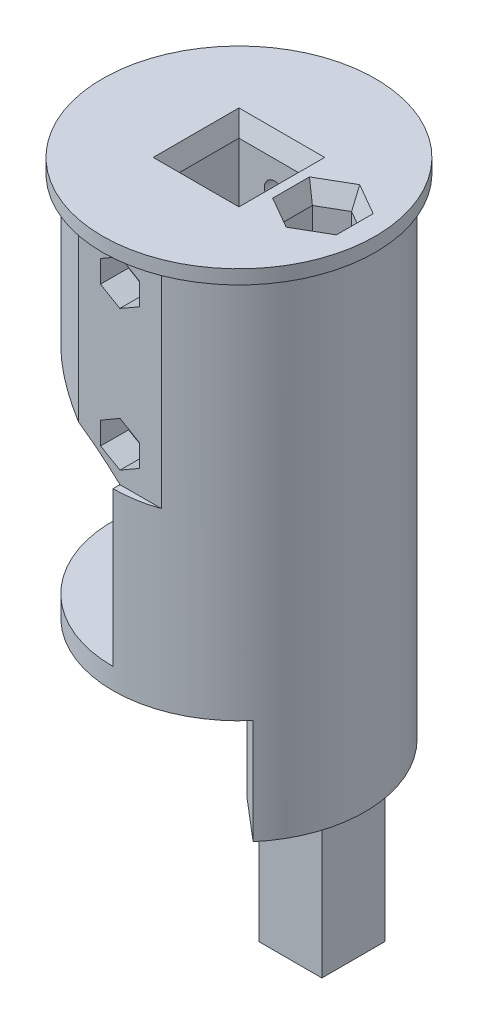
SolidWorks part; units mm, degrees
ref_plane "Спереди" through (0, 0, 0) normal (0, 0, 1) x (1, 0, 0)
ref_plane "Сверху" through (0, 0, 0) normal (0, 1, 0) x (1, 0, 0)
ref_plane "Справа" through (0, 0, 0) normal (1, 0, 0) x (0, 0, -1)
sketch "Эскиз1" plane through (0, 0, 0) normal (0, 1, 0) x (1, 0, 0)
  circle A0 centre (0, 0) radius 18
  dimension "D1" = 36
extrude "Бобышка-Вытянуть1" add sketch "Эскиз1" along normal blind 55
sketch "Эскиз2" plane through (0, 55, 0) normal (0, 1, 0) x (1, 0, 0)
  circle A0 centre (0, 0) radius 19.5
  dimension "D1" = 39
extrude "Бобышка-Вытянуть2" add sketch "Эскиз2" along normal blind 2
sketch "Эскиз3" plane through (0, 57, 0) normal (0, 1, 0) x (1, 0, 0)
  line L1 (-5.125, -5.125) -> (5.125, -5.125)
  line L2 (-5.125, -5.125) -> (-5.125, 5.125)
  line L3 (-5.125, 5.125) -> (5.125, 5.125)
  line L4 (5.125, -5.125) -> (5.125, 5.125)
  line L5 (-5.125, -5.125) -> (5.125, 5.125) construction
  line L6 (-5.125, 5.125) -> (5.125, -5.125) construction
  point P0 (0, 0)
  dimension "D1" = 10.25
extrude "Вырез-Вытянуть1" cut sketch "Эскиз3" against normal blind 40
sketch "Эскиз4" plane through (0, 0, 0) normal (0, -1, 0) x (1, 0, 0)
  line L0 (0, 0) -> (11.5702, 13.7888) construction
  line L1 (0, 0) -> (11.5702, -13.7888) construction
  line L2 (11.5702, 13.7888) -> (11.5702, -13.7888) construction
  line L3 (0, 0) -> (13.6996, 11.6756) construction
  line L5 (5.1423, -6.1284) -> (11.5702, -13.7888)
  line L6 (5.1423, -6.1284) -> (5.1423, 4.3826)
  line L7 (5.1423, 4.3826) -> (13.6996, 11.6756)
  circle A3 centre (0, 0) radius 18 construction
  arc A4 (13.6996, 11.6756) -> (11.5702, -13.7888) centre (0, 0) cw
  point P5 (11.5702, 13.7888)
  point P8 (11.5702, -13.7888)
  dimension "D1" = 100
  dimension "D2" = 3
  dimension "D3" = 10
extrude "Бобышка-Вытянуть3" add sketch "Эскиз4" along normal blind 15
sketch "Sketch1" plane through (0, -15, 0) normal (0, -1, 0) x (1, 0, 0)
  circle A0 centre (0, 0) radius 18
  arc A3 (13.6996, 11.6756) -> (11.5702, -13.7888) centre (0, 0) ccw construction
extrude "Boss-Extrude1" add sketch "Sketch1" along normal blind 20
sketch "Sketch3" plane through (0, -35, 0) normal (0, -1, 0) x (1, 0, 0)
  circle A0 centre (0, 0) radius 18
  circle A3 centre (0, 0) radius 18 construction
extrude "Boss-Extrude2" add sketch "Sketch3" along normal blind 7
sketch "Sketch4" plane through (0, -42, 0) normal (0, -1, 0) x (1, 0, 0)
  line L1 (5.1, 5.1) -> (-5.1, 5.1)
  line L2 (5.1, 5.1) -> (5.1, -5.1)
  line L3 (5.1, -5.1) -> (-5.1, -5.1)
  line L4 (-5.1, 5.1) -> (-5.1, -5.1)
  line L5 (5.1, 5.1) -> (-5.1, -5.1) construction
  line L6 (5.1, -5.1) -> (-5.1, 5.1) construction
  point P0 (0, 0)
  dimension "D1" = 10.2
  dimension "D2" = 10.2
extrude "Cut-Extrude2" cut sketch "Sketch4" against normal blind 27
sketch "Sketch6" plane through (0, 0, 0) normal (0, -1, 0) x (1, 0, 0)
  line L0 (0, 18) -> (0, -18) construction
  line L1 (0, 18) -> (0, -18)
  arc A0 (13.6996, 11.6756) -> (11.5702, -13.7888) centre (0, 0) ccw construction
  arc A1 (0, -18) -> (0, 18) centre (0, 0) cw
extrude "Cut-Extrude4" cut sketch "Sketch6" against normal blind 25
sketch "Sketch8" plane through (0, 0, 0) normal (0, -1, 0) x (1, 0, 0)
  line L0 (0, -18) -> (0, 18)
  arc A0 (0, -18) -> (0, 18) centre (0, 0) cw
  arc A1 (13.6996, 11.6756) -> (0, 18) centre (0, 0) ccw construction
extrude "Boss-Extrude3" add sketch "Sketch8" against normal blind 3
sketch "Sketch9" plane through (0, 0, 0) normal (-1, 0, 0) x (0, 0, 1)
  line L0 (-18, 3) -> (18, 25) construction
  line L2 (18, 25) -> (-18, 25)
  line L3 (18, 25) -> (18, 3)
  line L4 (18, 3) -> (-18, 3)
  line L5 (-18, 25) -> (-18, 3)
  line L6 (18, 25) -> (-18, 3) construction
  line L7 (18, 3) -> (-18, 25) construction
  point P4 (0, 14)
extrude "Cut-Extrude5" cut sketch "Sketch9" against normal blind 8
sketch "Sketch10" plane through (0, 0, 0) normal (0, -1, 0) x (1, 0, 0)
  line L0 (0, -18) -> (0, 18) construction
  line L2 (1.5, 8.7) -> (-1.5, 8.7)
  line L3 (1.5, 8.7) -> (1.5, 6.7)
  line L4 (1.5, 6.7) -> (-1.5, 6.7)
  line L5 (-1.5, 8.7) -> (-1.5, 6.7)
  line L6 (1.5, 8.7) -> (-1.5, 6.7) construction
  line L7 (1.5, 6.7) -> (-1.5, 8.7) construction
  circle A0 centre (0, 0) radius 3.7
  arc A1 (13.6996, 11.6756) -> (11.5702, -13.7888) centre (0, 0) ccw construction
  point P9 (0, 7.7)
  point P14 (0, 3.7)
  dimension "D1" = 7.4
  dimension "D2" = 2
  dimension "D3" = 3
  dimension "D4" = 4
extrude "Cut-Extrude6" cut sketch "Sketch10" against normal blind 10
sketch "Sketch11" plane through (0, -42, 0) normal (0, -1, 0) x (1, 0, 0)
  line L0 (-18, 0) -> (18, 0) construction
  circle A0 centre (0, 0) radius 18 construction
  circle A1 centre (12, 0) radius 2
  dimension "D1" = 4
  dimension "D2" = 6
extrude "Cut-Extrude7" cut sketch "Sketch11" against normal blind 102
sketch "Sketch15" plane through (0, -42, 0) normal (0, -1, 0) x (1, 0, 0)
  circle A0 centre (0, 0) radius 18
  circle A3 centre (0, 0) radius 18 construction
extrude "Cut-Extrude9" cut sketch "Sketch15" against normal blind 27
sketch "Sketch17" plane through (0, 25, 0) normal (0, -1, 0) x (1, 0, 0)
  line L2 (-18, 0) -> (14.8, 0) construction
  line L3 (14.8, 0) -> (13.8, 0) construction
  line L4 (0, 18) -> (0, -18) construction
  line L6 (5.9161, -17) -> (-5.9161, -17)
  line L7 (5.9161, 17) -> (-5.9161, 17)
  arc A0 (8, 16.1245) -> (8, -16.1245) centre (0, 0) ccw construction
  arc A1 (-5.9161, -17) -> (5.9161, -17) centre (0, 0) ccw
  arc A2 (-5.9161, 17) -> (5.9161, 17) centre (0, 0) cw
  point P14 (13.8, 0)
  point P20 (0, -17)
  point P23 (0, 17)
  dimension "D4" = 1
extrude "Cut-Extrude11" cut sketch "Sketch17" against normal blind 30
sketch "Sketch18" plane through (0, 0, -17) normal (0, 0, 1) x (1, 0, 0)
  line L0 (0, 25) -> (0, 55) construction
  line L1 (5.9161, 25) -> (-5.9161, 25) construction
  line L2 (5.9161, 55) -> (-5.9161, 55) construction
  circle A0 centre (0, 30) radius 1.5
  circle A1 centre (0, 50) radius 1.5
  point P3 (0, 40)
  dimension "D1" = 3
  dimension "D2" = 10
  dimension "D3" = 20
extrude "Cut-Extrude12" cut sketch "Sketch18" along normal through all
sketch "Sketch19" plane through (0, 0, -17) normal (0, 0, 1) x (1, 0, 0)
  circle A0 centre (0, 30) radius 3
  circle A1 centre (0, 50) radius 3
  dimension "D1" = 6
extrude "Cut-Extrude13" cut sketch "Sketch19" along normal blind 3
sketch "Sketch23" plane through (0, 3, 0) normal (0, 1, 0) x (1, 0, 0)
  line L0 (0, 18) -> (0, -18) construction
  line L1 (0, -14.4) -> (8, -14.4)
  line L2 (8, 16.1245) -> (8, -16.1245) construction
  line L3 (0, 14.4) -> (8, 14.4)
  line L4 (0, -14.4) -> (0, -18)
  line L5 (0, 14.4) -> (0, 18)
  line L6 (8, -14.4) -> (8, -16.1245)
  line L7 (8, 16.1245) -> (8, 14.4)
  arc A0 (8, 16.1245) -> (8, -16.1245) centre (0, 0) ccw construction
  arc A1 (0, -18) -> (8, -16.1245) centre (0, 0) ccw
  arc A2 (0, 18) -> (8, 16.1245) centre (0, 0) cw
  arc A3 (-5.9161, 17) -> (-5.9161, -17) centre (0, 0) ccw construction
  arc A4 (11.5702, 13.7888) -> (13.6996, -11.6756) centre (0, 0) ccw construction
  dimension "D1" = 3.6
extrude "Boss-Extrude5" add sketch "Sketch23" along normal blind 22
sketch "Sketch25" plane through (0, 0, 17) normal (0, 0, 1) x (1, 0, 0)
  line L0 (0, 55) -> (0, 25) construction
  line L1 (2.7713, 28.4) -> (2.7713, 31.6)
  line L2 (2.7713, 31.6) -> (0, 33.2)
  line L3 (0, 33.2) -> (-2.7713, 31.6)
  line L4 (-2.7713, 31.6) -> (-2.7713, 28.4)
  line L5 (-2.7713, 28.4) -> (0, 26.8)
  line L6 (0, 26.8) -> (2.7713, 28.4)
  line L7 (-5.9161, 55) -> (5.9161, 55) construction
  line L9 (-2.7821, 48.4189) -> (-0.0218, 46.8001)
  line L10 (-0.0218, 46.8001) -> (2.7603, 48.3811)
  line L11 (2.7603, 48.3811) -> (2.7821, 51.5811)
  line L12 (2.7821, 51.5811) -> (0.0218, 53.1999)
  line L13 (0.0218, 53.1999) -> (-2.7603, 51.6189)
  line L14 (-2.7603, 51.6189) -> (-2.7821, 48.4189)
  circle A0 centre (0, 30) radius 3.2 construction
  circle A1 centre (0, 50) radius 3.2 construction
  point P24 (0, 40)
  dimension "D1" = 6.4
  dimension "D2" = 20
  dimension "D3" = 10
extrude "Cut-Extrude16" cut sketch "Sketch25" against normal blind 4
sketch "Sketch26" plane through (0, 57, 0) normal (0, 1, 0) x (1, 0, 0)
  line L0 (14.8, 0) -> (5.125, 0) construction
  line L2 (8.4493, -2.05) -> (12, -4.1)
  line L3 (12, -4.1) -> (15.5507, -2.05)
  line L4 (15.5507, -2.05) -> (15.5507, 2.05)
  line L5 (15.5507, 2.05) -> (12, 4.1)
  line L6 (12, 4.1) -> (8.4493, 2.05)
  line L7 (5.125, -5.125) -> (5.125, 5.125) construction
  line L8 (8.4493, 2.05) -> (8.4493, -2.05)
  circle A0 centre (12, 0) radius 4.1 construction
  point P2 (15.5507, 0)
  dimension "D1" = 8.2
extrude "Cut-Extrude17" cut sketch "Sketch26" against normal blind 30
sketch "Sketch27" plane through (0, 0, 17) normal (0, 0, 1) x (1, 0, 0)
  line L0 (0, 25) -> (-20, 36.547) construction
  line L1 (-20, 36.547) -> (-20, 25)
  line L2 (-20, 25) -> (0, 25)
  line L3 (-18, 25) -> (-5.9161, 25) construction
  line L4 (-5.9161, 25) -> (0, 25) construction
  arc A0 (0, 25) -> (-20, 36.547) centre (-34.3242, -11.3572) ccw
  dimension "D3" = 50
  dimension "D1" = 30
  dimension "D2" = 20
extrude "Cut-Extrude18" cut sketch "Sketch27" against normal through all
fillet "Fillet2" radius 5 2 edges at (8, 14, 14.4) (8, 14, -14.4)
sketch "Sketch30" plane through (8, 0, 0) normal (-1, 0, 0) x (0, 0, 1)
  line L0 (-9.4, 8) -> (9.4, 8) construction
  line L1 (-9.4, 25) -> (-9.4, 3) construction
  line L2 (9.4, 3) -> (9.4, 25) construction
  line L4 (9.4, 13) -> (-9.4, 13)
  line L5 (9.4, 13) -> (9.4, 3)
  line L6 (9.4, 3) -> (-9.4, 3)
  line L7 (-9.4, 13) -> (-9.4, 3)
  line L8 (9.4, 13) -> (-9.4, 3) construction
  line L9 (9.4, 3) -> (-9.4, 13) construction
  point P6 (0, 8)
  dimension "D1" = 10
extrude "Cut-Extrude20" cut sketch "Sketch30" against normal blind 3
chamfer "Chamfer1" distance 1 angle 70 4 edges at (5.125, 57, 0) (0, 57, 5.125) (-5.125, 57, 0) (0, 57, -5.125) first distance on face at (12, 57, 0)
chamfer "Chamfer2" distance 1 angle 70 6 edges at (15.5507, 57, 0) (13.7754, 57, 3.075) (13.7754, 57, -3.075) (10.2246, 57, -3.075) (8.4493, 57, 0) (10.2246, 57, 3.075) first distance on face at (0, 57, 0)
sketch "Sketch37" plane through (0, -15, 0) normal (0, -1, 0) x (1, 0, 0)
  line L0 (5.1423, -0.8729) -> (17.9788, -0.8729) construction
  line L1 (5.1423, 4.3826) -> (5.1423, -6.1284) construction
  line L3 (15.4788, 3.6271) -> (6.4788, 3.6271)
  line L4 (15.4788, 3.6271) -> (15.4788, -5.3729)
  line L5 (15.4788, -5.3729) -> (6.4788, -5.3729)
  line L6 (6.4788, 3.6271) -> (6.4788, -5.3729)
  line L7 (15.4788, 3.6271) -> (6.4788, -5.3729) construction
  line L8 (15.4788, -5.3729) -> (6.4788, 3.6271) construction
  arc A0 (11.5702, -13.7888) -> (13.6996, 11.6756) centre (0, 0) ccw construction
  circle A1 centre (12, 0) radius 2
  point P8 (10.9788, -0.8729)
  dimension "D1" = 9
  dimension "D2" = 7
extrude "Boss-Extrude7" add sketch "Sketch37" along normal blind 20
sketch "Sketch38" plane through (0, -15, 0) normal (0, -1, 0) x (1, 0, 0)
  line L0 (5.1423, -6.1284) -> (5.1423, 4.3826)
  arc A0 (5.1423, -6.1284) -> (5.1423, 4.3826) centre (-10.9482, -0.8729) ccw
extrude "Cut-Extrude22" cut sketch "Sketch38" against normal up to surface (15 mm away) up to face at (0, 0, 7.7)
sketch "Sketch39" plane through (0, -15, 0) normal (0, -1, 0) x (1, 0, 0)
  line L0 (7.4207, -7.3729) -> (15.4207, -7.3729)
  line L1 (7.4207, -7.3729) -> (11.5989, -12.3522)
  line L2 (5.1423, -6.1284) -> (11.5702, -13.7888) construction
  line L3 (6.4788, -5.3729) -> (15.4788, -5.3729) construction
  line L4 (6.1866, -7.3729) -> (16.4207, -7.3729) construction
  arc A0 (11.5989, -12.3522) -> (15.4207, -7.3729) centre (-0.5503, 0.9293) ccw
  arc A1 (11.5702, -13.7888) -> (13.6996, 11.6756) centre (0, 0) ccw construction
  point P11 (11.4207, -7.3729)
  dimension "D1" = 8
  dimension "D2" = 2
  dimension "D3" = 6.5
  dimension "D4" = 5
  dimension "D6" = 50
extrude "Cut-Extrude23" cut sketch "Sketch39" against normal up to surface (28 mm away) up to face at (9.8333, 13, 0)
sketch "Sketch40" plane through (0, 3, 0) normal (0, 1, 0) x (1, 0, 0)
  line L0 (7.4207, 7.3729) -> (7.4207, 11.736)
  line L1 (7.4207, 11.736) -> (11.7839, 11.736)
  line L2 (11.7839, 11.736) -> (11.7839, 7.3729)
  line L3 (11.7839, 7.3729) -> (7.4207, 7.3729)
  line L4 (7.4207, 7.3729) -> (11, 7.3729) construction
  arc A1 (8, 9.4) -> (3, 14.4) centre (3, 9.4) ccw construction
extrude "Cut-Extrude24" cut sketch "Sketch40" along normal up to surface (10 mm away) up to face at (10.5956, 13, -3.0295)
fillet "Fillet7" radius 6 2 edges at (5.1423, -7.5, 4.3826) (5.1423, -7.5, -6.1284)
chamfer "Chamfer3" distance 3 angle 45 5 edges at (1.5, 25, 14.4) (1.5, 25, -14.4) (6.5355, 25, 12.9355) (6.5355, 25, -12.9355) (8, 25, 0)
